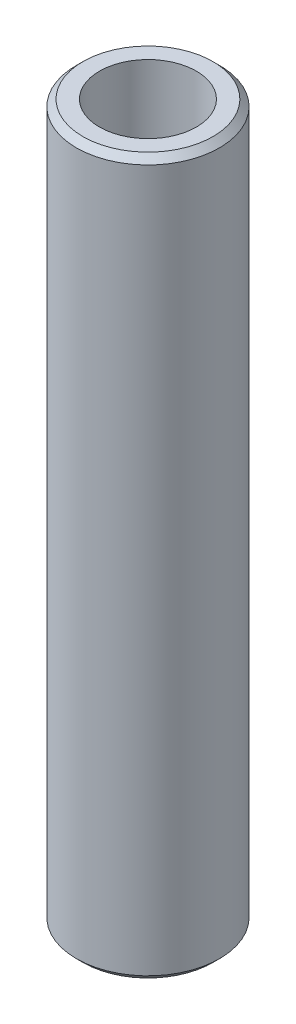
SolidWorks part; units mm, degrees
ref_plane "Front Plane" through (0, 0, 0) normal (0, 0, 1) x (1, 0, 0)
ref_plane "Top Plane" through (0, 0, 0) normal (0, 1, 0) x (1, 0, 0)
ref_plane "Right Plane" through (0, 0, 0) normal (1, 0, 0) x (0, 0, -1)
sketch "Sketch1" plane through (0, 0, 0) normal (0, 1, 0) x (1, 0, 0)
  circle A0 centre (0, 0) radius 60
  dimension "SHAFT_OD" = 120
extrude "Boss-Extrude1" add sketch "Sketch1" along normal blind 600
sketch "Sketch2" plane through (0, 0, 0) normal (0, 1, 0) x (1, 0, 0)
  circle A0 centre (0, 0) radius 40.6555
  dimension "BORE_D" = 81.3109
extrude "Cut-Extrude1" cut sketch "Sketch2" along normal through all
chamfer "Chamfer1" distance 5.455 angle 45 2 edges at (0, 600, 60) (0, 0, 60)
